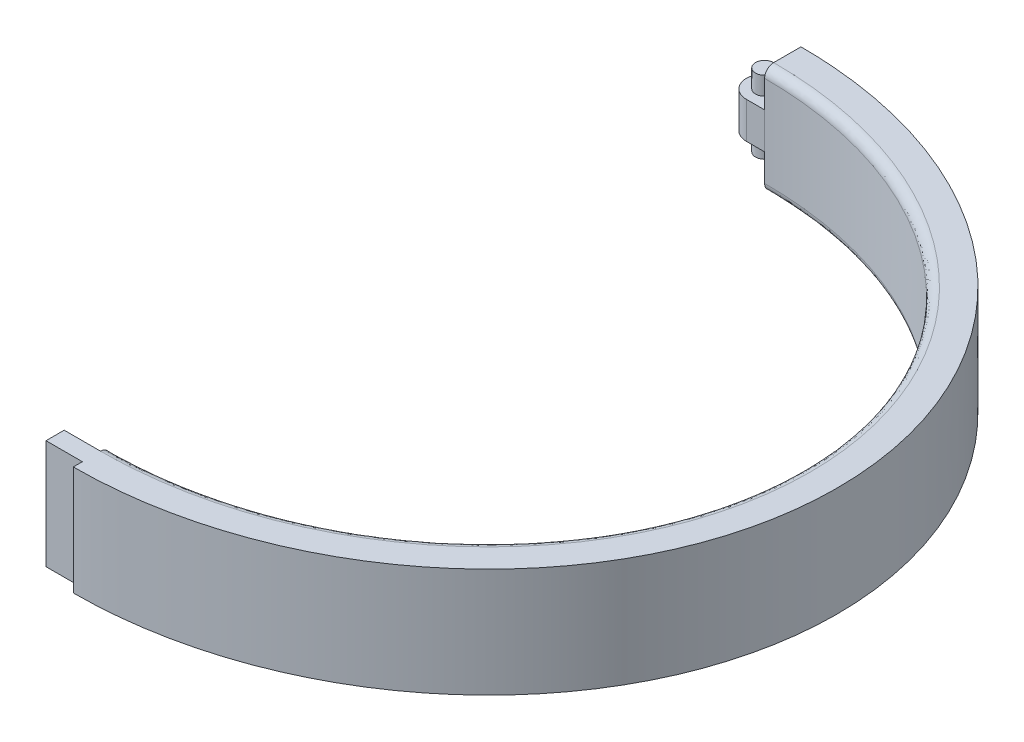
SolidWorks part; units mm, degrees
ref_plane "Front Plane" through (0, 0, 0) normal (0, 0, 1) x (1, 0, 0)
ref_plane "Top Plane" through (0, 0, 0) normal (0, 1, 0) x (1, 0, 0)
ref_plane "Right Plane" through (0, 0, 0) normal (1, 0, 0) x (0, 0, -1)
sketch "Sketch1" plane through (0, 0, 0) normal (0, 1, 0) x (1, 0, 0)
  line L0 (0, 100) -> (0, 90)
  line L1 (0, -90) -> (0, -100)
  ellipse E0 centre (0, 0) end of major axis (-100, 0) minor radius 90 (0, -90) -> (0, 90) ccw
  ellipse E1 centre (0, 0) end of major axis (110, 0) minor radius 100 (0, -100) -> (0, 100) ccw
extrude "Boss-Extrude1" add sketch "Sketch1" along normal blind 30
sketch "Sketch2" plane through (0, 0, 0) normal (-1, 0, 0) x (0, 0, 1)
  line L0 (-100, 30) -> (-100, 0) construction
  line L1 (-100, 20) -> (-90, 20)
  line L2 (-100, 20) -> (-100, 10)
  line L3 (-100, 10) -> (-90, 10)
  line L4 (-90, 20) -> (-90, 10)
  line L5 (-90, 30) -> (-90, 0) construction
  line L6 (-100, 30) -> (-90, 30) construction
  dimension "D1" = 10
  dimension "D2" = 10
extrude "Boss-Extrude2" add sketch "Sketch2" along normal blind 10
sketch "Sketch3" plane through (0, 10, 0) normal (0, -1, 0) x (1, 0, 0)
  circle A0 centre (-5, -95) radius 2.5
  dimension "D1" = 5
extrude "Boss-Extrude3" add sketch "Sketch3" along normal blind 5 and the other way blind 15
sketch "Sketch4" plane through (0, 0, 0) normal (-1, 0, 0) x (0, 0, 1)
  line L0 (90, 30) -> (100, 30) construction
  line L1 (92.5, 30) -> (97.5, 30)
  line L2 (92.5, 30) -> (92.5, 0)
  line L3 (92.5, 0) -> (97.5, 0)
  line L4 (97.5, 30) -> (97.5, 0)
  line L5 (90, 0) -> (100, 0) construction
  line L6 (100, 30) -> (100, 0) construction
  dimension "D1" = 5
  dimension "D2" = 2.5
extrude "Boss-Extrude4" add sketch "Sketch4" along normal blind 10
fillet "Fillet2" radius 5 2 edges at (-10, 15, -100) (-10, 15, -90)
fillet "Fillet1" radius 2.5 2 edges at (100, 0, 0) (100, 30, 0)
